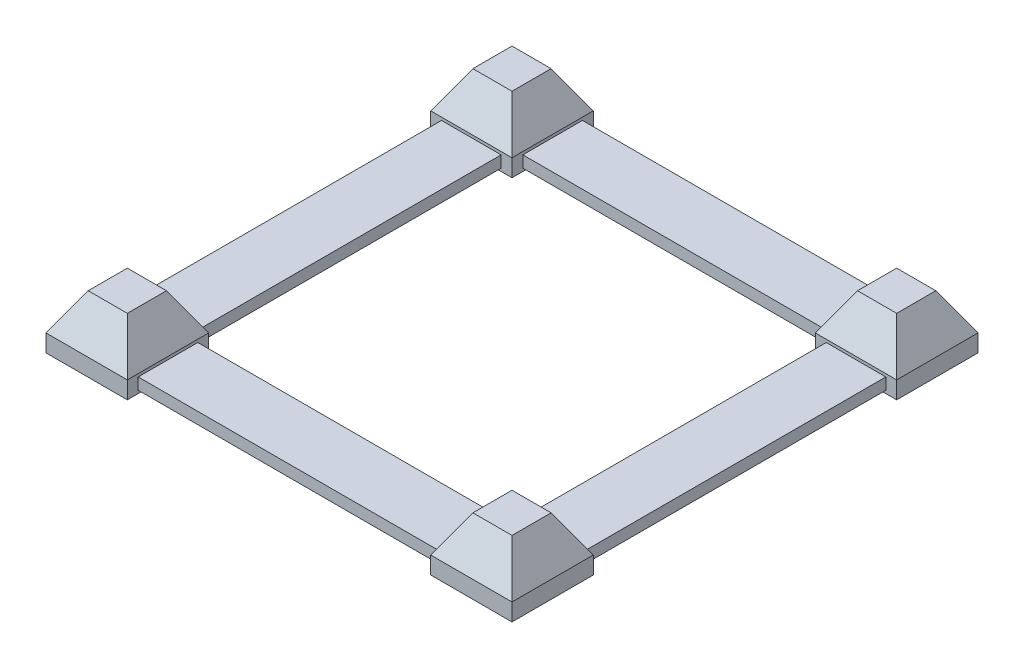
SolidWorks part; units mm, degrees
ref_plane "Front Plane" through (0, 0, 0) normal (0, 0, 1) x (1, 0, 0)
ref_plane "Top Plane" through (0, 0, 0) normal (0, 1, 0) x (1, 0, 0)
ref_plane "Right Plane" through (0, 0, 0) normal (1, 0, 0) x (0, 0, -1)
sketch "Sketch2" plane through (0, 0, 0) normal (0, 1, 0) x (1, 0, 0)
  line L0 (490, -425.6697) -> (490, -475)
  line L1 (490, -475) -> (510, -475)
  line L2 (-510, -425.6697) -> (-510, -475)
  line L3 (510, -425.6697) -> (510, -475)
  line L4 (574.3303, -510) -> (525, -510)
  line L5 (574.3303, -490) -> (525, -490)
  line L6 (525, -490) -> (525, -510)
  line L7 (490, -574.3303) -> (490, -525)
  line L8 (510, -574.3303) -> (510, -525)
  line L9 (510, -525) -> (490, -525)
  line L10 (425.6697, -490) -> (475, -490)
  line L11 (425.6697, -510) -> (475, -510)
  line L12 (475, -510) -> (475, -490)
  line L13 (500, -425) -> (500, -475) construction
  line L14 (490, 574.3303) -> (490, 525)
  line L15 (490, 525) -> (510, 525)
  line L16 (510, 574.3303) -> (510, 525)
  line L17 (574.3303, 490) -> (525, 490)
  line L18 (574.3303, 510) -> (525, 510)
  line L19 (525, 510) -> (525, 490)
  line L20 (490, 425.6697) -> (490, 475)
  line L21 (510, 425.6697) -> (510, 475)
  line L22 (510, 475) -> (490, 475)
  line L23 (425.6697, 510) -> (475, 510)
  line L24 (425.6697, 490) -> (475, 490)
  line L25 (475, 490) -> (475, 510)
  line L26 (500, 575) -> (500, 525) construction
  line L27 (-510, -475) -> (-490, -475)
  line L28 (-490, -425.6697) -> (-490, -475)
  line L29 (-425.6697, -510) -> (-475, -510)
  line L30 (-425.6697, -490) -> (-475, -490)
  line L31 (-475, -490) -> (-475, -510)
  line L32 (-510, -574.3303) -> (-510, -525)
  line L33 (-490, -574.3303) -> (-490, -525)
  line L34 (-490, -525) -> (-510, -525)
  line L35 (-574.3303, -490) -> (-525, -490)
  line L36 (-574.3303, -510) -> (-525, -510)
  line L37 (-525, -510) -> (-525, -490)
  line L38 (-510, 574.3303) -> (-510, 525)
  line L39 (-510, 525) -> (-490, 525)
  line L40 (-490, 574.3303) -> (-490, 525)
  line L41 (-425.6697, 490) -> (-475, 490)
  line L42 (-425.6697, 510) -> (-475, 510)
  line L43 (-475, 510) -> (-475, 490)
  line L44 (-510, 425.6697) -> (-510, 475)
  line L45 (-490, 425.6697) -> (-490, 475)
  line L46 (-490, 475) -> (-510, 475)
  line L47 (-574.3303, 510) -> (-525, 510)
  line L48 (-574.3303, 490) -> (-525, 490)
  line L49 (-525, 490) -> (-525, 510)
  line L50 (-500, -425) -> (-500, -475) construction
  line L51 (-500, 575) -> (-500, 525) construction
  line L52 (-605.7125, 605.7125) -> (-394.2875, 605.7125)
  line L53 (-605.7125, 605.7125) -> (-605.7125, 394.2875)
  line L54 (-605.7125, 394.2875) -> (-394.2875, 394.2875)
  line L55 (-394.2875, 605.7125) -> (-394.2875, 394.2875)
  line L56 (-605.7125, 605.7125) -> (-394.2875, 394.2875) construction
  line L57 (-605.7125, 394.2875) -> (-394.2875, 605.7125) construction
  line L58 (-605.7125, -394.2875) -> (-394.2875, -394.2875)
  line L59 (-605.7125, -394.2875) -> (-605.7125, -605.7125)
  line L60 (-605.7125, -605.7125) -> (-394.2875, -605.7125)
  line L61 (-394.2875, -394.2875) -> (-394.2875, -605.7125)
  line L62 (-605.7125, -394.2875) -> (-394.2875, -605.7125) construction
  line L63 (-605.7125, -605.7125) -> (-394.2875, -394.2875) construction
  line L64 (605.7125, 605.7125) -> (394.2875, 605.7125)
  line L65 (605.7125, 605.7125) -> (605.7125, 394.2875)
  line L66 (605.7125, 394.2875) -> (394.2875, 394.2875)
  line L67 (394.2875, 605.7125) -> (394.2875, 394.2875)
  line L68 (605.7125, 605.7125) -> (394.2875, 394.2875) construction
  line L69 (605.7125, 394.2875) -> (394.2875, 605.7125) construction
  line L70 (605.7125, -394.2875) -> (394.2875, -394.2875)
  line L71 (605.7125, -394.2875) -> (605.7125, -605.7125)
  line L72 (605.7125, -605.7125) -> (394.2875, -605.7125)
  line L73 (394.2875, -394.2875) -> (394.2875, -605.7125)
  line L74 (605.7125, -394.2875) -> (394.2875, -605.7125) construction
  line L75 (605.7125, -605.7125) -> (394.2875, -394.2875) construction
  arc A0 (490, -425.6697) -> (425.6697, -490) centre (500, -500) ccw
  arc A1 (425.6697, -510) -> (490, -574.3303) centre (500, -500) ccw
  arc A2 (510, -574.3303) -> (574.3303, -510) centre (500, -500) ccw
  arc A3 (574.3303, -490) -> (510, -425.6697) centre (500, -500) ccw
  arc A4 (490, -425.6697) -> (529.2889, -430.9554) centre (500, -500) cw
  arc A5 (490, 574.3303) -> (425.6697, 510) centre (500, 500) ccw
  arc A6 (425.6697, 490) -> (490, 425.6697) centre (500, 500) ccw
  arc A7 (510, 425.6697) -> (574.3303, 490) centre (500, 500) ccw
  arc A8 (574.3303, 510) -> (510, 574.3303) centre (500, 500) ccw
  arc A9 (490, 574.3303) -> (529.2889, 569.0446) centre (500, 500) cw
  arc A10 (-510, -425.6697) -> (-574.3303, -490) centre (-500, -500) ccw
  arc A11 (-574.3303, -510) -> (-510, -574.3303) centre (-500, -500) ccw
  arc A12 (-490, -574.3303) -> (-425.6697, -510) centre (-500, -500) ccw
  arc A13 (-425.6697, -490) -> (-490, -425.6697) centre (-500, -500) ccw
  arc A14 (-510, -425.6697) -> (-470.7111, -430.9554) centre (-500, -500) cw
  arc A15 (-510, 574.3303) -> (-574.3303, 510) centre (-500, 500) ccw
  arc A16 (-574.3303, 490) -> (-510, 425.6697) centre (-500, 500) ccw
  arc A17 (-490, 425.6697) -> (-425.6697, 490) centre (-500, 500) ccw
  arc A18 (-425.6697, 510) -> (-490, 574.3303) centre (-500, 500) ccw
  arc A19 (-510, 574.3303) -> (-470.7111, 569.0446) centre (-500, 500) cw
  circle A20 centre (0, 0) radius 157.4996
  point P22 (-500, -500)
  point P24 (-500, -500)
  point P48 (500, -500)
  point P49 (500, -500)
  point P71 (500, 500)
  point P72 (500, 500)
  point P87 (-500, 500)
  point P88 (-500, 500)
extrude "Boss-Extrude1" add sketch "Sketch2" along normal blind 60 contours L55 L52 L53 L54 A15 A19 A18 L42 L43 L41 A17 L45 L46 L44 A16 L48 L49 L47 | L64 L67 L66 L65 A5 A9 A8 L18 L19 L17 A7 L21 L22 L20 A6 L24 L25 L23 | L70 L73 L72 L71 A0 A4 A3 L5 L6 L4 A2 L8 L9 L7 A1 L11 L12 L10 | L61 L58 L59 L60 A10 A14 A13 L30 L31 L29 A12 L33 L34 L32 A11 L36 L37 L35 | A14 L2 L27 L28 | A4 L0 L1 L3 | A9 L14 L15 L16 | A19 L38 L39 L40 region at (500, 0, 450.111) region at (-500, 0, 450.111) region at (500, 0, -549.889) region at (-500, 0, -549.889) region at (-500, 0, -602.7225) region at (-500, 0, 397.2775) region at (602.7225, 0, -500) region at (602.7225, 0, 500)
chamfer "Chamfer1" distance 15 angle 45 4 edges at (-500, 0, -605.7125) (-394.2875, 0, -500) (-500, 0, -394.2875) (-605.7125, 0, -500)
chamfer "Chamfer2" distance 15 angle 45 4 edges at (605.7125, 0, -500) (500, 0, -394.2875) (394.2875, 0, -500) (500, 0, -605.7125)
chamfer "Chamfer3" distance 15 angle 45 4 edges at (605.7125, 0, 500) (500, 0, 605.7125) (394.2875, 0, 500) (500, 0, 394.2875)
chamfer "Chamfer4" distance 15 angle 45 4 edges at (-605.7125, 0, 500) (-500, 0, 605.7125) (-394.2875, 0, 500) (-500, 0, 394.2875)
sketch "Sketch3" plane through (0, 0, 394.2875) normal (0, 0, -1) x (-1, 0, 0)
  line L0 (-500, 60) -> (-500, 15) construction
  line L1 (-605.7125, 60) -> (-394.2875, 60) construction
  line L2 (-605.7125, 15) -> (-394.2875, 15) construction
  line L4 (-577.5, 52.5) -> (-422.5, 52.5)
  line L5 (-577.5, 52.5) -> (-577.5, 22.5)
  line L6 (-577.5, 22.5) -> (-422.5, 22.5)
  line L7 (-422.5, 52.5) -> (-422.5, 22.5)
  line L8 (-577.5, 52.5) -> (-422.5, 22.5) construction
  line L9 (-577.5, 22.5) -> (-422.5, 52.5) construction
  point P6 (-500, 37.5)
extrude "Boss-Extrude2" add sketch "Sketch3" along normal up to surface (788.5751 mm away) up to face at (500, 37.5, -394.2875)
sketch "Sketch5" plane through (394.2875, 0, 0) normal (-1, 0, 0) x (0, 0, 1)
  line L0 (-500, 60) -> (-500, 15) construction
  line L1 (-605.7125, 60) -> (-394.2875, 60) construction
  line L2 (-605.7125, 15) -> (-394.2875, 15) construction
  line L4 (-577.5, 22.5) -> (-422.5, 22.5)
  line L5 (-577.5, 22.5) -> (-577.5, 52.5)
  line L6 (-577.5, 52.5) -> (-422.5, 52.5)
  line L7 (-422.5, 22.5) -> (-422.5, 52.5)
  line L8 (-577.5, 22.5) -> (-422.5, 52.5) construction
  line L9 (-577.5, 52.5) -> (-422.5, 22.5) construction
  point P6 (-500, 37.5)
extrude "Boss-Extrude3" add sketch "Sketch5" along normal up to next (788.5751 mm away) contours L4 L7 L6 L5 region at (394.2875, 37.5, -500)
pattern_linear "LPattern1" count 2 spacing 1000 along (-1, 0, 0) of "Boss-Extrude2"
pattern_linear "LPattern2" count 2 spacing 1000 along (0, 0, 1) of "Boss-Extrude3"
sketch "Sketch6" plane through (0, 60, 0) normal (0, 1, 0) x (1, 0, 0)
  line L1 (-605.7125, 605.7125) -> (-394.2875, 605.7125)
  line L2 (-605.7125, 605.7125) -> (-605.7125, 394.2875)
  line L3 (-605.7125, 394.2875) -> (-394.2875, 394.2875)
  line L4 (-394.2875, 605.7125) -> (-394.2875, 394.2875)
  line L5 (-605.7125, 605.7125) -> (-394.2875, 394.2875) construction
  line L6 (-605.7125, 394.2875) -> (-394.2875, 605.7125) construction
  point P0 (-500, 500)
extrude "Boss-Extrude4" add sketch "Sketch6" along normal blind 95 draft 30
pattern_linear "LPattern3" count 2 spacing 1000 along (1, 0, 0) count 2 spacing 1000 along (0, 0, 1) of "Boss-Extrude4"
sketch "Sketch7" plane through (0, 0, 0) normal (0, 0, 1) x (1, 0, 0)
  line L0 (0, 999.5654) -> (130, 999.5654)
  line L1 (130, 999.5654) -> (283.9091, 576.7037)
  line L2 (283.9091, 576.7037) -> (605.3029, 193.6815)
  line L3 (605.3029, 193.6815) -> (553.9779, 150.6147)
  line L4 (0, 1195.4824) -> (0, 821.9339) construction
  line L5 (183.9795, 851.2579) -> (97.0667, 819.6243) construction
  line L6 (43.2559, 999.5654) -> (43.2559, 937.2282) construction
  dimension "D1" = 160
